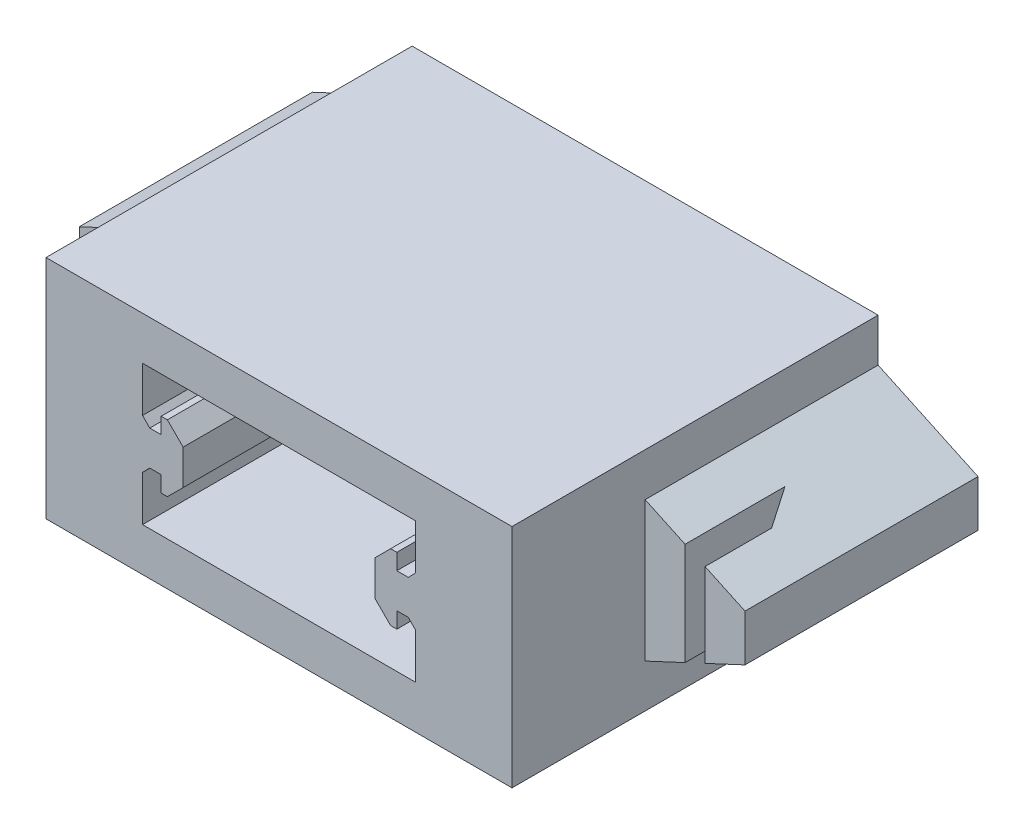
SolidWorks part; units mm, degrees
ref_plane "Front Plane" through (0, 0, 0) normal (0, 0, 1) x (1, 0, 0)
ref_plane "Top Plane" through (0, 0, 0) normal (0, 1, 0) x (1, 0, 0)
ref_plane "Right Plane" through (0, 0, 0) normal (1, 0, 0) x (0, 0, -1)
sketch "Sketch1" plane through (0, 0, 118.9397) normal (0, 0, 1) x (1, 0, 0)
  line L0 (-32.7804, 27.347) -> (-32.7804, 22.647) construction
  line L1 (-47.7804, 35.847) -> (22.2196, 35.847)
  line L2 (-47.7804, 35.847) -> (-47.7804, 1.847)
  line L3 (-47.7804, 1.847) -> (22.2196, 1.847)
  line L4 (22.2196, 35.847) -> (22.2196, 1.847)
  line L5 (-31.2804, 28.847) -> (-26.5804, 28.847) construction
  line L6 (-31.2804, 8.847) -> (-26.5804, 8.847) construction
  line L7 (7.2196, 15.047) -> (7.2196, 10.347) construction
  line L8 (-12.7804, 28.847) -> (-12.7804, 7.4462) construction
  line L9 (-14.2804, 28.847) -> (-11.2804, 28.847) construction
  line L10 (-47.7804, 18.847) -> (-11.2453, 18.847) construction
  line L11 (-33.2804, 29.347) -> (-33.2804, 22.5477)
  line L12 (-33.2804, 22.5477) -> (-32.1987, 21.447)
  line L13 (-32.1987, 21.447) -> (-30.4804, 21.447)
  line L14 (-30.4804, 21.447) -> (-30.4804, 23.847)
  line L15 (-30.4804, 23.847) -> (-29.5482, 23.847)
  line L16 (-29.5482, 23.847) -> (-27.1804, 21.4792)
  line L17 (-27.1804, 21.4792) -> (-27.1804, 16.2147)
  line L18 (-33.2804, 29.347) -> (7.7196, 29.347)
  line L20 (-26.739, 21.7449) -> (-29.341, 24.347) construction
  line L21 (-30.9804, 24.147) -> (-30.9804, 21.947) construction
  line L22 (-29.341, 24.347) -> (-30.7804, 24.347) construction
  line L23 (-26.6804, 21.6035) -> (-26.6804, 16.0905) construction
  line L24 (-30.9804, 21.947) -> (-32.0804, 21.947) construction
  line L26 (-29.5482, 13.847) -> (-27.1804, 16.2147)
  line L27 (-30.4804, 13.847) -> (-29.5482, 13.847)
  line L28 (-30.4804, 16.247) -> (-30.4804, 13.847)
  line L29 (-32.1987, 16.247) -> (-30.4804, 16.247)
  line L30 (-33.2804, 15.1463) -> (-32.1987, 16.247)
  line L31 (-33.2804, 8.347) -> (-33.2804, 15.1463)
  line L32 (-33.2804, 8.347) -> (7.7196, 8.347)
  line L33 (7.7196, 8.347) -> (7.7196, 15.1463)
  line L34 (7.7196, 15.1463) -> (6.6379, 16.247)
  line L35 (6.6379, 16.247) -> (4.9196, 16.247)
  line L36 (4.9196, 16.247) -> (4.9196, 13.847)
  line L37 (4.9196, 13.847) -> (3.9874, 13.847)
  line L38 (3.9874, 13.847) -> (1.6196, 16.2147)
  line L39 (1.6196, 21.4792) -> (1.6196, 16.2147)
  line L40 (3.9874, 23.847) -> (1.6196, 21.4792)
  line L41 (4.9196, 23.847) -> (3.9874, 23.847)
  line L42 (4.9196, 21.447) -> (4.9196, 23.847)
  line L43 (6.6379, 21.447) -> (4.9196, 21.447)
  line L44 (7.7196, 22.5477) -> (6.6379, 21.447)
  line L45 (7.7196, 29.347) -> (7.7196, 22.5477)
  point P55 (-12.7804, 18.847)
  dimension "D1" = 15
  dimension "D2" = 7
  dimension "D3" = 7
  dimension "D4" = 15
  dimension "D5" = 0.5
  dimension "D6" = 0.5
  dimension "D7" = 0.5
  dimension "D8" = 0.5
  dimension "D9" = 0.5
  dimension "D10" = 0.5
  dimension "D11" = 0.5
  dimension "D12" = 0.5
  dimension "D13" = 1.5433
extrude "Boss-Extrude1" add sketch "Sketch1" against normal blind 45 contours L2 L1 L4 L3 | L32 L33 L34 L35 L36 L37 L38 L39 L40 L41 L42 L43 L44 L45 L18 L11 L12 L13 L14 L15 L16 L17 L26 L27 L28 L29 L30 L31
sketch "Sketch2" plane through (22.2196, 0, 0) normal (1, 0, 0) x (0, 0, -1)
  line L0 (-73.9397, 35.847) -> (-73.9397, 1.847) construction
  line L1 (-73.9397, 22.347) -> (-98.9397, 22.347)
  line L2 (-73.9397, 22.347) -> (-73.9397, 15.347)
  line L3 (-73.9397, 15.347) -> (-98.9397, 15.347)
  line L4 (-98.9397, 22.347) -> (-98.9397, 15.347)
  line L5 (-73.9397, 18.847) -> (-118.9397, 18.847) construction
  line L6 (-118.9397, 35.847) -> (-118.9397, 1.847) construction
  point P10 (-73.9397, 18.847)
  dimension "D1" = 7
  dimension "D2" = 25
  dimension "D3" = 0
extrude "Boss-Extrude2" add sketch "Sketch2" along normal blind 15
sketch "Sketch4" plane through (0, 0, 73.9397) normal (0, 0, -1) x (-1, 0, 0)
  line L0 (-37.2196, 22.347) -> (-22.2196, 29.347)
  line L1 (-22.2196, 35.847) -> (-22.2196, 22.347) construction
  line L2 (-22.2196, 29.347) -> (-22.2196, 22.347)
  line L3 (-22.2196, 22.347) -> (-37.2196, 22.347)
  line L4 (-37.2196, 18.847) -> (-20.3313, 18.847) construction
  line L5 (-37.2196, 15.347) -> (-37.2196, 22.347) construction
  line L6 (-22.2196, 8.347) -> (-22.2196, 15.347)
  line L7 (-37.2196, 15.347) -> (-22.2196, 8.347)
  line L8 (-22.2196, 15.347) -> (-37.2196, 15.347)
  dimension "D1" = 7
extrude "Boss-Extrude3" add sketch "Sketch4" against normal up to vertex (25 mm away) up to point (37.2196, 22.347, 98.9397)
sketch "Sketch7" plane through (-47.7804, 0, 0) normal (-1, 0, 0) x (0, 0, 1)
  line L0 (73.9397, 35.847) -> (73.9397, 1.847) construction
  line L1 (73.9397, 15.347) -> (98.9397, 15.347)
  line L2 (73.9397, 15.347) -> (73.9397, 22.347)
  line L3 (73.9397, 22.347) -> (98.9397, 22.347)
  line L4 (98.9397, 15.347) -> (98.9397, 22.347)
  point P6 (73.9397, 18.847)
  point P7 (73.9397, 18.847)
  dimension "D1" = 7
  dimension "D2" = 25
  dimension "D3" = 0
extrude "Boss-Extrude4" add sketch "Sketch7" along normal blind 15
sketch "Sketch8" plane through (0, 0, 73.9397) normal (0, 0, -1) x (-1, 0, 0)
  line L0 (47.7804, 15.347) -> (47.7804, 8.347)
  line L1 (47.7804, 15.347) -> (47.7804, 1.847) construction
  line L2 (47.7804, 8.347) -> (62.7804, 15.347)
  line L3 (62.7804, 15.347) -> (47.7804, 15.347)
  line L4 (62.7804, 18.847) -> (47.7804, 18.847) construction
  line L5 (62.7804, 22.347) -> (62.7804, 15.347) construction
  line L6 (47.7804, 29.347) -> (62.7804, 22.347)
  line L7 (47.7804, 22.347) -> (47.7804, 29.347)
  line L8 (62.7804, 22.347) -> (47.7804, 22.347)
  dimension "D1" = 7
extrude "Boss-Extrude5" add sketch "Sketch8" against normal up to vertex (25 mm away) up to point (-62.7804, 15.347, 98.9397)
sketch "Sketch5" plane through (0, 35.847, 0) normal (0, 1, 0) x (1, 0, 0)
  line L0 (22.2196, -98.9397) -> (37.2196, -98.9397) construction
  line L5 (29.7196, -73.9397) -> (29.7196, -98.9397) construction
  line L6 (22.2196, -73.9397) -> (37.2196, -73.9397) construction
  line L7 (28.2196, -83.9397) -> (31.2196, -88.9397)
  line L8 (31.2196, -88.9397) -> (31.2196, -98.9397)
  line L9 (31.2196, -98.9397) -> (28.2196, -98.9397)
  line L10 (28.2196, -98.9397) -> (28.2196, -83.9397)
  line L11 (-12.7804, -73.9397) -> (-12.7804, -118.9397) construction
  line L12 (-47.7804, -73.9397) -> (22.2196, -73.9397) construction
  line L13 (-47.7804, -118.9397) -> (22.2196, -118.9397) construction
  line L14 (-56.7804, -98.9397) -> (-53.7804, -98.9397)
  line L15 (-53.7804, -83.9397) -> (-56.7804, -88.9397)
  line L16 (-56.7804, -88.9397) -> (-56.7804, -98.9397)
  line L17 (-53.7804, -98.9397) -> (-53.7804, -83.9397)
  point P2 (29.7196, -98.9397)
  dimension "D1" = 3
  dimension "D2" = 10
  dimension "D3" = 15
  dimension "D4" = 0
extrude "Cut-Extrude2" cut sketch "Sketch5" against normal blind 55
sketch "Sketch9" plane through (0, 0, 73.9397) normal (0, 0, -1) x (-1, 0, 0)
  line L0 (-22.2196, 8.347) -> (-37.2196, 15.347)
  line L1 (-37.2196, 15.347) -> (-37.2196, 22.347)
  line L2 (-37.2196, 22.347) -> (-22.2196, 29.347)
  line L3 (-22.2196, 29.347) -> (-22.2196, 35.847)
  line L4 (-22.2196, 35.847) -> (47.7804, 35.847)
  line L5 (47.7804, 35.847) -> (47.7804, 29.347)
  line L6 (47.7804, 29.347) -> (62.7804, 22.347)
  line L7 (62.7804, 22.347) -> (62.7804, 15.347)
  line L8 (62.7804, 15.347) -> (47.7804, 8.347)
  line L9 (47.7804, 8.347) -> (47.7804, 1.847)
  line L10 (47.7804, 1.847) -> (-22.2196, 1.847)
  line L11 (-22.2196, 1.847) -> (-22.2196, 8.347)
extrude "Boss-Extrude6" add sketch "Sketch9" along normal blind 10
